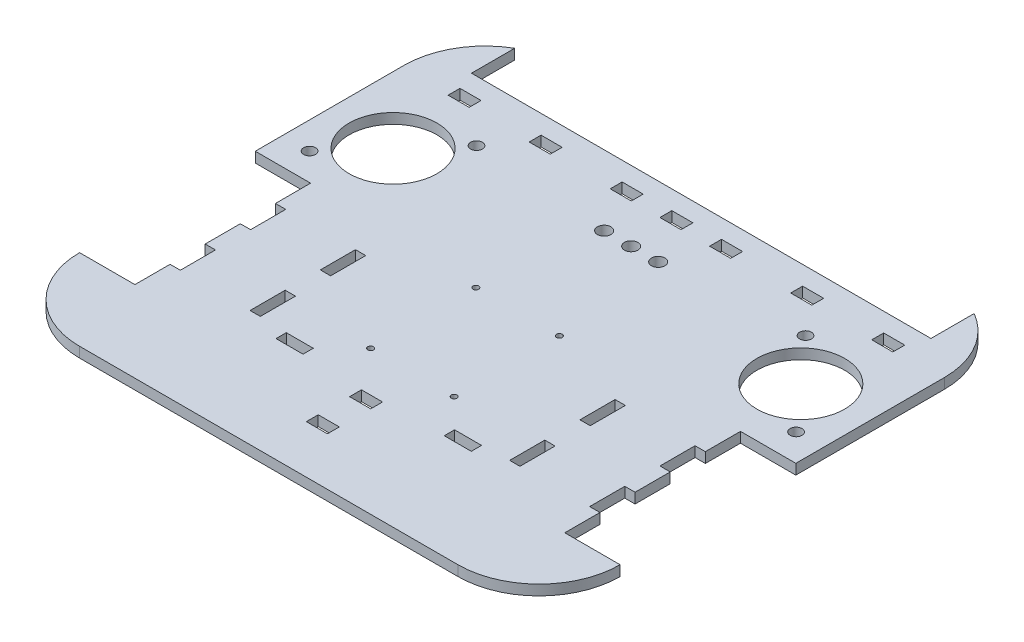
SolidWorks part; units mm, degrees
ref_plane "Front Plane" through (0, 0, 0) normal (0, 0, 1) x (1, 0, 0)
ref_plane "Top Plane" through (0, 0, 0) normal (0, 1, 0) x (1, 0, 0)
ref_plane "Right Plane" through (0, 0, 0) normal (1, 0, 0) x (0, 0, -1)
sketch "Sketch1" plane through (0, 0, 0) normal (0, 1, 0) x (1, 0, 0)
  line L1 (-127, 114.3) -> (127, 114.3)
  line L2 (-127, 114.3) -> (-127, -114.3)
  line L3 (-127, -114.3) -> (127, -114.3)
  line L4 (127, 114.3) -> (127, -114.3)
  line L5 (-127, 114.3) -> (127, -114.3) construction
  line L6 (-127, -114.3) -> (127, 114.3) construction
  point P0 (0, 0)
  dimension "D1" = 254
  dimension "D2" = 228.6
extrude "Boss-Extrude1" add sketch "Sketch1" along normal blind 4.826
sketch "Sketch2" plane through (0, 4.826, 0) normal (0, 1, 0) x (1, 0, 0)
  line L0 (-127, 114.3) -> (-127, -114.3) construction
  line L1 (-127, 6.35) -> (-101, 6.35)
  line L2 (-127, 6.35) -> (-127, -76.2)
  line L3 (-127, -76.2) -> (-101, -76.2)
  line L4 (-101, 6.35) -> (-101, -76.2)
  line L5 (127, -114.3) -> (127, 114.3) construction
  line L6 (127, 6.35) -> (101, 6.35)
  line L7 (127, 6.35) -> (127, -76.2)
  line L8 (127, -76.2) -> (101, -76.2)
  line L9 (101, 6.35) -> (101, -76.2)
  line L10 (-127, -114.3) -> (127, -114.3) construction
  dimension "D1" = 38.1
  dimension "D2" = 38.1
  dimension "D3" = 82.55
  dimension "D4" = 82.55
  dimension "D5" = 26
  dimension "D6" = 26
extrude "Cut-Extrude1" cut sketch "Sketch2" against normal blind 4.826
sketch "Sketch4" plane through (0, 4.826, 0) normal (0, 1, 0) x (1, 0, 0)
  line L0 (0, -114.3) -> (0, 114.3) construction
  line L1 (-127, -114.3) -> (127, -114.3) construction
  line L2 (127, 114.3) -> (-127, 114.3) construction
  line L3 (-127, 76.2) -> (-88.9, 76.2) construction
  line L4 (-127, 114.3) -> (-127, 6.35) construction
  line L5 (-88.9, 76.2) -> (-88.9, 114.3) construction
  line L6 (-127, 76.2) -> (-127, 114.3)
  line L7 (-127, 114.3) -> (-88.9, 114.3)
  line L8 (127, 76.2) -> (127, 114.3)
  line L9 (127, 114.3) -> (88.9, 114.3)
  arc A0 (-127, 76.2) -> (-88.9, 114.3) centre (-88.9, 76.2) cw
  arc A1 (127, 76.2) -> (88.9, 114.3) centre (88.9, 76.2) ccw
  dimension "D1" = 38.1
  dimension "D2" = 38.1
extrude "Cut-Extrude3" cut sketch "Sketch4" against normal blind 4.826
sketch "Sketch7" plane through (0, 4.826, 0) normal (0, 1, 0) x (1, 0, 0)
  line L0 (0, -114.3) -> (0, 114.3) construction
  line L1 (-127, -114.3) -> (127, -114.3) construction
  line L2 (88.9, 114.3) -> (-88.9, 114.3) construction
  line L3 (107.95, 88.9) -> (107.95, 114.3)
  line L4 (107.95, 88.9) -> (-107.95, 88.9)
  line L5 (0, 88.9) -> (0, 114.3)
  line L6 (107.95, 114.3) -> (-107.95, 114.3)
  line L7 (-107.95, 88.9) -> (-107.95, 114.3)
  line M6 (88.9, 114.3) -> (-88.9, 114.3)
  dimension "D2" = 107.95
extrude "Cut-Extrude5" cut sketch "Sketch7" against normal blind 4.826 contours L7 L4 L5 M6 | L5 L4 L3 M6 region at (53.975, 4.826, -101.6) region at (-53.975, 4.826, -101.6)
sketch "Sketch8" plane through (0, 4.826, 0) normal (0, 1, 0) x (1, 0, 0)
  line L0 (-127, -76.2) -> (-88.9, -76.2) construction
  line L1 (-88.9, -76.2) -> (-88.9, -114.3) construction
  line L2 (-127, -114.3) -> (127, -114.3) construction
  line L3 (-127, -76.2) -> (-127, -114.3)
  line L4 (-127, -114.3) -> (-88.9, -114.3)
  line L5 (0, -114.3) -> (0, 88.9) construction
  line L6 (107.95, 88.9) -> (-107.95, 88.9) construction
  line L7 (127, -114.3) -> (88.9, -114.3)
  line L8 (127, -76.2) -> (127, -114.3)
  arc A0 (-127, -76.2) -> (-88.9, -114.3) centre (-88.9, -76.2) ccw
  arc A1 (127, -76.2) -> (88.9, -114.3) centre (88.9, -76.2) cw
  dimension "D1" = 38.1
extrude "Cut-Extrude6" cut sketch "Sketch8" against normal blind 4.826
sketch "Sketch10" plane through (0, 4.826, 0) normal (0, 1, 0) x (1, 0, 0)
  line L0 (-101, -76.2) -> (-101, 6.35) construction
  line L1 (-101, -10.16) -> (-96.174, -10.16)
  line L2 (-101, -10.16) -> (-101, -26.67)
  line L3 (-101, -26.67) -> (-96.174, -26.67)
  line L4 (-96.174, -10.16) -> (-96.174, -26.67)
  line L5 (101, 6.35) -> (101, -76.2) construction
  line L6 (-101, -43.18) -> (-96.174, -43.18)
  line L7 (-101, -43.18) -> (-101, -59.69)
  line L8 (-101, -59.69) -> (-96.174, -59.69)
  line L9 (-96.174, -43.18) -> (-96.174, -59.69)
  line L10 (101, -10.16) -> (96.174, -10.16)
  line L11 (101, -10.16) -> (101, -26.67)
  line L12 (101, -26.67) -> (96.174, -26.67)
  line L13 (96.174, -10.16) -> (96.174, -26.67)
  line L14 (-101, 6.35) -> (-96.174, 6.35) construction
  line L15 (101, -43.18) -> (96.174, -43.18)
  line L16 (101, -43.18) -> (101, -59.69)
  line L17 (101, -59.69) -> (96.174, -59.69)
  line L18 (96.174, -43.18) -> (96.174, -59.69)
  line L19 (-96.174, 6.35) -> (-96.174, -10.16) construction
  line L20 (-96.174, -26.67) -> (-96.174, -43.18) construction
  line L21 (-96.174, -43.18) -> (-83.474, -80.9089) construction
  line L22 (-101, -76.2) -> (-96.174, -76.2)
  line L23 (-96.174, -76.2) -> (-96.174, -59.69)
  line L24 (-96.174, -59.69) -> (-83.474, -98.2941)
  line L25 (101, -76.2) -> (96.174, -76.2)
  line L26 (96.174, -76.2) -> (96.174, -59.69)
  line L27 (96.174, -43.18) -> (96.174, -26.67)
  line L28 (101, 6.35) -> (96.174, 6.35)
  line L29 (96.174, 6.35) -> (96.174, -10.16)
  line M19 (101, -76.2) -> (101, 6.35)
  line M35 (-101, 6.35) -> (-101, -76.2)
  dimension "D1" = 4.826
  dimension "D2" = 4.826
extrude "Cut-Extrude8" cut sketch "Sketch10" against normal through all contours L9 L6 L8 M35 | L10 L13 L12 M19 | L15 L18 L17 M19 | L2 L3 L4 L1 region at (-98.587, 4.826, 51.435) region at (98.587, 4.826, 18.415) region at (98.587, 4.826, 51.435)
sketch "Sketch12" plane through (0, 0, 0) normal (0, -1, 0) x (1, 0, 0)
  line L0 (-58.582, 43.18) -> (-58.582, 59.69) construction
  line L1 (-58.582, 43.18) -> (-63.408, 43.18) construction
  line L2 (-63.408, 43.18) -> (-63.408, 59.69) construction
  line L3 (-58.582, 59.69) -> (-63.408, 59.69) construction
  line L4 (-58.582, 26.67) -> (-63.408, 26.67) construction
  line L5 (-58.582, 10.16) -> (-58.582, 26.67) construction
  line L6 (-58.582, 10.16) -> (-63.408, 10.16) construction
  line L7 (-63.408, 10.16) -> (-63.408, 26.67) construction
  line L8 (-58.582, 43.18) -> (-58.582, 59.69)
  line L9 (-58.582, 43.18) -> (-63.408, 43.18)
  line L10 (-63.408, 43.18) -> (-63.408, 59.69)
  line L11 (-58.582, 59.69) -> (-63.408, 59.69)
  line L12 (-58.582, 26.67) -> (-63.408, 26.67)
  line L13 (-58.582, 10.16) -> (-58.582, 26.67)
  line L14 (-58.582, 10.16) -> (-63.408, 10.16)
  line L15 (-63.408, 10.16) -> (-63.408, 26.67)
extrude "Cut-Extrude9" cut sketch "Sketch12" against normal through all
sketch "Sketch13" plane through (0, 4.826, 0) normal (0, 1, 0) x (1, 0, 0)
  line L0 (63.408, -43.18) -> (63.408, -59.69) construction
  line L1 (63.408, -43.18) -> (58.582, -43.18) construction
  line L2 (58.582, -43.18) -> (58.582, -59.69) construction
  line L3 (63.408, -59.69) -> (58.582, -59.69) construction
  line L4 (63.408, -26.67) -> (58.582, -26.67) construction
  line L5 (63.408, -10.16) -> (63.408, -26.67) construction
  line L6 (63.408, -10.16) -> (58.582, -10.16) construction
  line L7 (58.582, -10.16) -> (58.582, -26.67) construction
  line L8 (63.408, -43.18) -> (63.408, -59.69)
  line L9 (63.408, -43.18) -> (58.582, -43.18)
  line L10 (58.582, -43.18) -> (58.582, -59.69)
  line L11 (63.408, -59.69) -> (58.582, -59.69)
  line L12 (63.408, -26.67) -> (58.582, -26.67)
  line L13 (63.408, -10.16) -> (63.408, -26.67)
  line L14 (63.408, -10.16) -> (58.582, -10.16)
  line L15 (58.582, -10.16) -> (58.582, -26.67)
extrude "Cut-Extrude10" cut sketch "Sketch13" against normal through all
sketch "Sketch14" plane through (0, 4.826, 0) normal (0, 1, 0) x (1, 0, 0)
  line L0 (-127, 6.35) -> (127, 6.35) construction
  line L1 (0, 6.35) -> (0, -114.3) construction
  line L2 (-88.9, -114.3) -> (88.9, -114.3) construction
  line L3 (-22.86, 6.35) -> (-22.86, -114.3) construction
  line L4 (22.86, 6.35) -> (22.86, -114.3) construction
  dimension "D1" = 22.86
sketch "Sketch15" plane through (0, 4.826, 0) normal (0, 1, 0) x (1, 0, 0)
  circle A0 centre (19.5961, 2.6692) radius 1.3462 construction
  circle A1 centre (-19.6723, 2.6692) radius 1.3462 construction
  circle A2 centre (-19.6723, -46.7636) radius 1.3462 construction
  circle A3 centre (19.5961, -46.7636) radius 1.3462 construction
  circle A4 centre (19.5961, 2.6692) radius 1.3462
  circle A5 centre (-19.6723, 2.6692) radius 1.3462
  circle A6 centre (-19.6723, -46.7636) radius 1.3462
  circle A7 centre (19.5961, -46.7636) radius 1.3462
extrude "Cut-Extrude11" cut sketch "Sketch15" against normal through all
sketch "Sketch16" plane through (0, 4.826, 0) normal (0, 1, 0) x (1, 0, 0)
  line L0 (0, 88.9) -> (0, -114.3) construction
  line L1 (107.95, 88.9) -> (-107.95, 88.9) construction
  circle A0 centre (77.2939, 60.6102) radius 2.7781 construction
  circle A1 centre (114.3, 19.1646) radius 2.7781 construction
  circle A2 centre (95.7969, 39.8874) radius 20.6375 construction
  circle A3 centre (77.2939, 60.6102) radius 2.7781
  circle A4 centre (114.3, 19.1646) radius 2.7781
  circle A5 centre (95.7969, 39.8874) radius 20.6375
  circle A6 centre (-95.7969, 39.8874) radius 20.6375
  circle A7 centre (-77.2939, 60.6102) radius 2.7781
  circle A8 centre (-114.3, 19.1646) radius 2.7781
extrude "Cut-Extrude12" cut sketch "Sketch16" against normal through all
sketch "Sketch17" plane through (0, 4.826, 0) normal (0, 1, 0) x (1, 0, 0)
  line L0 (-56.4929, 80.0388) -> (-56.4929, 74.4508)
  line L1 (-104.4989, 80.0388) -> (-94.5929, 80.0388)
  line L2 (-104.4989, 80.0388) -> (-104.4989, 74.4508)
  line L3 (-104.4989, 74.4508) -> (-94.5929, 74.4508)
  line L4 (-94.5929, 80.0388) -> (-94.5929, 74.4508)
  line L9 (-66.3989, 80.0388) -> (-56.4929, 80.0388)
  line L10 (-66.3989, 80.0388) -> (-66.3989, 74.4508)
  line L11 (-66.3989, 74.4508) -> (-56.4929, 74.4508)
  line L12 (-18.3929, 80.0388) -> (-18.3929, 74.4508)
  line L13 (-28.2989, 80.0388) -> (-18.3929, 80.0388)
  line L14 (-28.2989, 80.0388) -> (-28.2989, 74.4508)
  line L15 (-28.2989, 74.4508) -> (-18.3929, 74.4508)
  line L16 (-127, 76.2) -> (-127, 6.35) construction
  line L17 (0, 88.9) -> (0, -114.3)
  line L18 (107.95, 88.9) -> (-107.95, 88.9) construction
  line L19 (-94.5929, 74.4508) -> (-78.3377, 74.4508) construction
  line L20 (18.3929, 80.0388) -> (18.3929, 74.4508)
  line L21 (28.2989, 80.0388) -> (18.3929, 80.0388)
  line L22 (28.2989, 80.0388) -> (28.2989, 74.4508)
  line L23 (28.2989, 74.4508) -> (18.3929, 74.4508)
  line L24 (56.4929, 80.0388) -> (56.4929, 74.4508)
  line L25 (66.3989, 74.4508) -> (56.4929, 74.4508)
  line L26 (66.3989, 80.0388) -> (66.3989, 74.4508)
  line L27 (66.3989, 80.0388) -> (56.4929, 80.0388)
  line L28 (104.4989, 80.0388) -> (94.5929, 80.0388)
  line L29 (104.4989, 80.0388) -> (104.4989, 74.4508)
  line L30 (104.4989, 74.4508) -> (94.5929, 74.4508)
  line L31 (94.5929, 80.0388) -> (94.5929, 74.4508)
  line L36 (4.953, 74.4508) -> (4.953, 80.0388)
  line L37 (4.953, 74.4508) -> (-4.953, 74.4508)
  line L38 (4.953, 80.0388) -> (-4.953, 80.0388)
  line L39 (-4.953, 74.4508) -> (-4.953, 80.0388)
  line L40 (4.953, 74.4508) -> (-4.953, 80.0388) construction
  line L41 (4.953, 80.0388) -> (-4.953, 74.4508) construction
  point P42 (0, 77.2448)
  dimension "D1" = 9.906
  dimension "D2" = 5.588
  dimension "D6" = 3
  dimension "D7" = 22.5011
  dimension "D8" = 9.906
  dimension "D9" = 0
extrude "Cut-Extrude13" cut sketch "Sketch17" against normal through all contours L28 L31 L30 L29 | L26 L27 L24 L25 | L23 L22 L21 L20 | L36 L38 L17 L37 | L39 L37 L17 L38 | L14 L15 L12 L13 | L10 L11 L0 L9 | L4 L1 L2 L3 region at (-61.4459, 4.826, -77.2448) region at (-99.5459, 4.826, -77.2448) region at (-23.3459, 4.826, -77.2448) region at (2.4765, 4.826, -77.2448) region at (-2.4765, 4.826, -77.2448) region at (23.3459, 4.826, -77.2448) region at (61.4459, 4.826, -77.2448) region at (99.5459, 4.826, -77.2448)
sketch "Sketch18" plane through (0, 4.826, 0) normal (0, 1, 0) x (1, 0, 0)
  line L0 (-4.953, -91.694) -> (4.953, -91.694)
  line L1 (-4.953, -91.694) -> (-4.953, -86.106)
  line L2 (4.953, -91.694) -> (4.953, -86.106)
  line L3 (-4.953, -86.106) -> (4.953, -86.106)
  line L4 (-4.953, -91.694) -> (4.953, -86.106) construction
  line L5 (4.953, -91.694) -> (-4.953, -86.106) construction
  line L6 (0, 6.35) -> (0, -114.3) construction
  line L7 (-4.953, -71.374) -> (4.953, -71.374)
  line L8 (-4.953, -71.374) -> (-4.953, -65.786)
  line L9 (4.953, -71.374) -> (4.953, -65.786)
  line L10 (-4.953, -65.786) -> (4.953, -65.786)
  line L11 (-4.953, -71.374) -> (4.953, -65.786) construction
  line L12 (4.953, -71.374) -> (-4.953, -65.786) construction
  point P1 (0, -88.9)
  point P10 (0, -68.58)
  dimension "D1" = 9.906
  dimension "D2" = 5.588
  dimension "D3" = 0
  dimension "D4" = 25.4
  dimension "D5" = 2
extrude "Cut-Extrude14" cut sketch "Sketch18" against normal through all
sketch "Sketch19" plane through (0, 4.826, 0) normal (0, 1, 0) x (1, 0, 0)
  circle A0 centre (0, 55.982) radius 3.175
  circle A1 centre (12.7, 55.982) radius 3.175
  circle A2 centre (-12.7, 55.982) radius 3.175
  dimension "D1" = 6.35
  dimension "D2" = 2
  dimension "D3" = 2
extrude "Cut-Extrude15" cut sketch "Sketch19" against normal through all
sketch "Sketch22" plane through (0, 0, 0) normal (0, -1, 0) x (1, 0, 0)
  line L0 (-33.182, 60.198) -> (-45.882, 60.198) construction
  line L1 (-33.182, 60.198) -> (-33.182, 65.024) construction
  line L2 (-33.182, 65.024) -> (-45.882, 65.024) construction
  line L3 (-45.882, 60.198) -> (-45.882, 65.024) construction
  line L4 (33.182, 60.198) -> (45.882, 60.198) construction
  line L5 (45.882, 65.024) -> (45.882, 60.198) construction
  line L6 (33.182, 65.024) -> (45.882, 65.024) construction
  line L7 (33.182, 65.024) -> (33.182, 60.198) construction
  line L8 (-33.182, 60.198) -> (-45.882, 60.198)
  line L9 (-33.182, 60.198) -> (-33.182, 65.024)
  line L10 (-33.182, 65.024) -> (-45.882, 65.024)
  line L11 (-45.882, 60.198) -> (-45.882, 65.024)
  line L12 (33.182, 60.198) -> (45.882, 60.198)
  line L13 (45.882, 65.024) -> (45.882, 60.198)
  line L14 (33.182, 65.024) -> (45.882, 65.024)
  line L15 (33.182, 65.024) -> (33.182, 60.198)
extrude "Cut-Extrude18" cut sketch "Sketch22" against normal through all
equation "\"MDF\"= 0.19in"
equation "\"GenDiameter\"= 60mm"
equation "\"GenCutDiameter\" = 1.8in"
equation "\"GenCutDistance\" = 1"
equation "\"TowerHeight\" = 6in"
equation "\"TowerFrontBase\" = 3in"
equation "\"FunnelHeight\" = 1in"
equation "\"FunnelAngle\" = 20"
equation "\"TowerSideBase\" = 3in"
equation "\"BaseLength\" = 9in"
equation "\"BaseWidth\" = 10in"
equation "\"WheelHoleLength\" = 3.25in"
equation "\"WheelHoleWidth\" = 26mm"
equation "\"DropLength\" = 1in"
equation "\"D1@Sketch1\"=\"BaseWidth\""
equation "\"D2@Sketch1\"=\"BaseLength\""
equation "\"D1@Boss-Extrude1\"=\"MDF\""
equation "\"WheelHoleFromBack\" = 1.5in"
equation "\"D1@Sketch2\"=\"WheelHoleFromBack\""
equation "\"D2@Sketch2\"=\"WheelHoleFromBack\""
equation "\"D3@Sketch2\"=\"WheelHoleLength\""
equation "\"D4@Sketch2\"=\"WheelHoleLength\""
equation "\"D5@Sketch2\"=\"WheelHoleWidth\""
equation "\"D6@Sketch2\"=\"WheelHoleWidth\""
equation "\"D1@Cut-Extrude1\"=\"MDF\""
equation "\"DropWidth\" = 8.5in"
equation "\"BumperWidth\" = 2in"
equation "\"D2@Sketch4\"=\"WheelHoleFromBack\""
equation "\"D1@Cut-Extrude3\"=\"MDF\""
equation "\"D1@Sketch7\"=\"DropLength\""
equation "\"D2@Sketch7\"=\"DropWidth\"/2"
equation "\"D1@Cut-Extrude5\"=\"MDF\""
equation "\"D1@Cut-Extrude6\"=\"MDF\""
equation "\"D1@Sketch10\"=\"MDF\""
equation "\"D2@Sketch10\"=\"MDF\""
